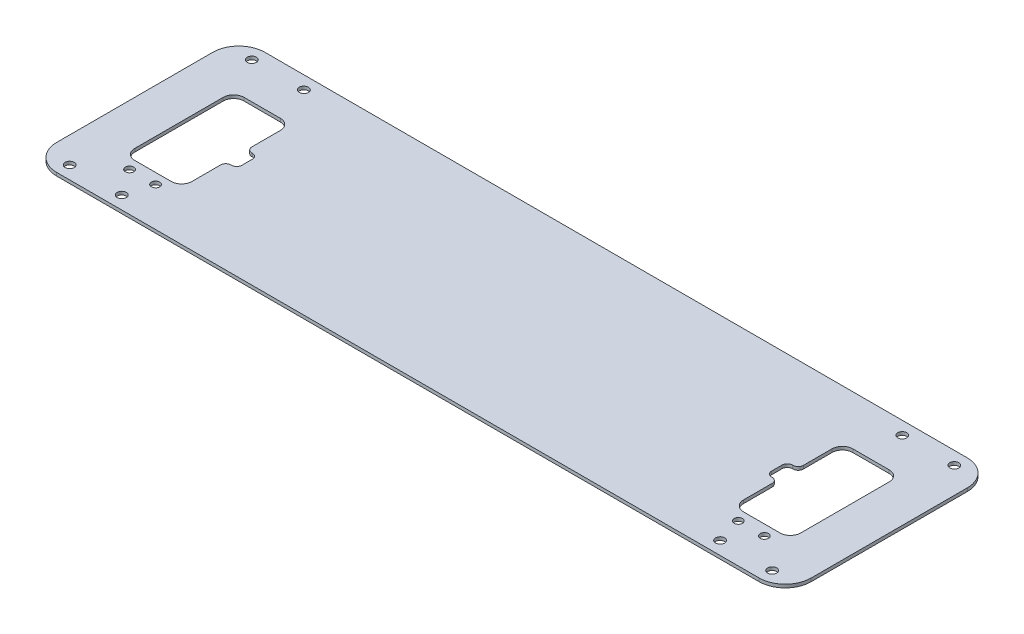
SolidWorks part; units mm, degrees
ref_plane "Front Plane" through (0, 0, 0) normal (0, 0, 1) x (1, 0, 0)
ref_plane "Top Plane" through (0, 0, 0) normal (0, 1, 0) x (1, 0, 0)
ref_plane "Right Plane" through (0, 0, 0) normal (1, 0, 0) x (0, 0, -1)
sketch "Sketch1" plane through (0, 0, 0) normal (0, 1, 0) x (1, 0, 0)
  line L0 (128.27, 0) -> (-128.27, 0) construction
  line L1 (184.15, 50.8) -> (-184.15, 50.8)
  line L2 (184.15, 50.8) -> (184.15, -50.8)
  line L3 (184.15, -50.8) -> (-184.15, -50.8)
  line L4 (-184.15, 50.8) -> (-184.15, -50.8)
  line L5 (184.15, 50.8) -> (-184.15, -50.8) construction
  line L6 (184.15, -50.8) -> (-184.15, 50.8) construction
  line L7 (-128.27, 0) -> (-128.27, 17.78) construction
  line L8 (-128.27, 17.78) -> (-134.62, 17.78) construction
  line L9 (-128.27, -20.32) -> (-134.62, -20.32) construction
  line L12 (-162.56, -26.67) -> (-162.56, 26.67)
  line L15 (-134.62, -26.67) -> (-162.56, -26.67)
  line L17 (-134.62, 26.67) -> (-162.56, 26.67)
  line L18 (0, 50.8) -> (0, -50.8) construction
  line L19 (-134.62, 26.67) -> (-134.62, -26.67)
  line L20 (-162.56, 17.78) -> (-168.91, 17.78) construction
  line L21 (128.27, 17.78) -> (134.62, 17.78) construction
  line L22 (162.56, 17.78) -> (168.91, 17.78) construction
  line L23 (-162.56, -17.78) -> (-168.91, -17.78) construction
  line L24 (134.62, 26.67) -> (162.56, 26.67)
  line L25 (128.27, 17.78) -> (128.27, -20.32) construction
  line L26 (128.27, -20.32) -> (134.62, -20.32) construction
  line L27 (134.62, 26.67) -> (134.62, -26.67)
  line L28 (134.62, -26.67) -> (162.56, -26.67)
  line L29 (162.56, -26.67) -> (162.56, 26.67)
  line L30 (162.56, -17.78) -> (168.91, -17.78) construction
  line L31 (184.15, -31.75) -> (154.94, -31.75) construction
  line L32 (146.05, 44.45) -> (184.15, 44.45) construction
  line L33 (154.94, -31.75) -> (142.24, -31.75) construction
  line L34 (146.05, -44.45) -> (184.15, -44.45) construction
  line L35 (-146.05, -44.45) -> (-184.15, -44.45) construction
  line L36 (-146.05, 44.45) -> (-184.15, 44.45) construction
  line L37 (-128.27, 0) -> (-128.27, -20.32) construction
  line L38 (-184.15, -31.75) -> (-154.94, -31.75) construction
  line L39 (-154.94, -31.75) -> (-142.24, -31.75) construction
  line L40 (-134.62, 5.08) -> (-129.286, 5.08)
  line L41 (-129.286, 5.08) -> (-129.286, -5.08)
  line L42 (-129.286, -5.08) -> (-134.62, -5.08)
  line L43 (134.62, 5.08) -> (129.286, 5.08)
  line L44 (129.286, 5.08) -> (129.286, -5.08)
  line L45 (129.286, -5.08) -> (134.62, -5.08)
  circle A0 centre (-128.27, 17.78) radius 2.032 construction
  circle A1 centre (-128.27, -20.32) radius 2.032 construction
  circle A2 centre (-168.91, 17.78) radius 2.032 construction
  circle A3 centre (-168.91, -17.78) radius 2.032 construction
  circle A4 centre (168.91, 17.78) radius 2.032 construction
  circle A5 centre (128.27, 17.78) radius 2.032 construction
  circle A6 centre (128.27, -20.32) radius 2.032 construction
  circle A7 centre (168.91, -17.78) radius 2.032 construction
  circle A8 centre (171.45, -44.45) radius 2.2225
  circle A9 centre (146.05, -44.45) radius 2.2225
  circle A10 centre (171.45, 44.45) radius 2.2225
  circle A11 centre (146.05, 44.45) radius 2.2225
  circle A12 centre (-146.05, -44.45) radius 2.2225
  circle A13 centre (-171.45, -44.45) radius 2.2225
  circle A14 centre (-146.05, 44.45) radius 2.2225
  circle A15 centre (-171.45, 44.45) radius 2.2225
  circle A16 centre (142.24, -31.75) radius 2.032
  circle A17 centre (154.94, -31.75) radius 2.032
  circle A18 centre (-154.94, -31.75) radius 2.032
  circle A19 centre (-142.24, -31.75) radius 2.032
  point P0 (0, 0)
  point P11 (-128.27, 0)
  point P13 (-134.62, 17.78)
  point P17 (-134.62, -20.32)
  point P37 (0, 0)
  point P50 (171.45, 44.45)
  point P51 (146.05, 44.45)
  point P56 (171.45, -44.45)
  point P57 (146.05, -44.45)
  point P84 (-131.953, 5.08)
  point P87 (131.953, 5.08)
  dimension "D5" = 4.064
  dimension "D6" = 8.89
  dimension "D18" = 4.445
  dimension "D1" = 368.3
  dimension "D2" = 101.6
  dimension "D3" = 128.27
  dimension "D4" = 38.1
  dimension "D7" = 6.35
  dimension "D8" = 27.94
  dimension "D9" = 53.34
  dimension "D10" = 8.89
  dimension "D11" = 6.35
  dimension "D12" = 8.89
  dimension "D13" = 15.24
  dimension "D14" = 12.7
  dimension "D15" = 38.1
  dimension "D16" = 12.7
  dimension "D17" = 38.1
  dimension "D19" = 17.78
  dimension "D20" = 6.35
  dimension "D21" = 6.35
  dimension "D22" = 19.05
  dimension "D23" = 29.21
  dimension "D24" = 12.7
  dimension "D25" = 7.62
  dimension "D26" = 7.62
  dimension "D27" = 5.334
  dimension "D28" = 10.16
  dimension "D29" = 21.59
extrude "Boss-Extrude1" add sketch "Sketch1" along normal blind 1.5875 contours L1 L4 L3 L2 A18 A17 A16 A14 A12 A11 A10 A9 A8 L45 L44 L43 L27 L24 L29 L28 L41 L42 L19 L15 L12 L17 L40 A13 A15 A19 region at (0, 0, -0.0482)
fillet "Fillet1" radius 5.08 4 edges at (-134.62, 0.7937, 26.67) (-162.56, 0.7937, 26.67) (-162.56, 0.7937, -26.67) (-134.62, 0.7937, -26.67)
fillet "Fillet2" radius 5.08 4 edges at (162.56, 0.7937, 26.67) (134.62, 0.7937, 26.67) (134.62, 0.7937, -26.67) (162.56, 0.7937, -26.67)
fillet "Fillet3" radius 12.7 4 edges at (184.15, 0.7937, 50.8) (184.15, 0.7937, -50.8) (-184.15, 0.7937, 50.8) (-184.15, 0.7937, -50.8)
fillet "Fillet4" radius 2.54 8 edges at (-129.286, 0.7937, 5.08) (-129.286, 0.7937, -5.08) (129.286, 0.7937, 5.08) (129.286, 0.7937, -5.08) (134.62, 0.7937, 5.08) (134.62, 0.7937, -5.08) (-134.62, 0.7937, 5.08) (-134.62, 0.7937, -5.08)
